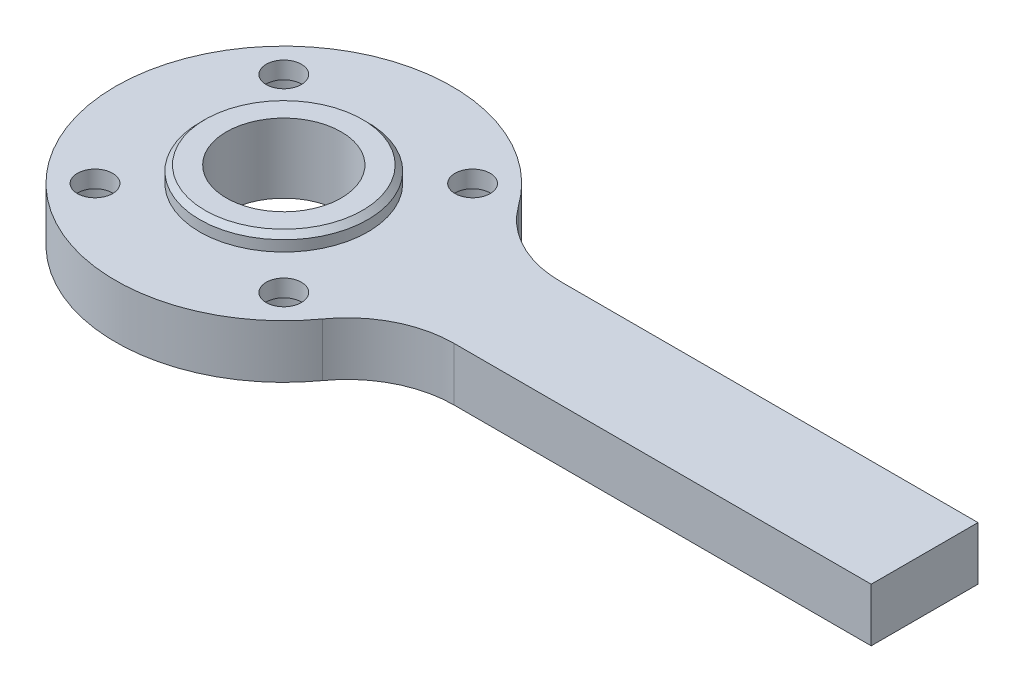
SolidWorks part; units mm, degrees
ref_plane "前视基准面" through (0, 0, 0) normal (0, 0, 1) x (1, 0, 0)
ref_plane "上视基准面" through (0, 0, 0) normal (0, 1, 0) x (1, 0, 0)
ref_plane "右视基准面" through (0, 0, 0) normal (1, 0, 0) x (0, 0, -1)
sketch "草图2" plane through (0, 0, 0) normal (0, 1, 0) x (1, 0, 0)
  circle A0 centre (0, 0) radius 31.5
  dimension "D1" = 63
extrude "凸台-拉伸1" add sketch "草图2" along normal blind 10
sketch "草图3" plane through (0, 10, 0) normal (0, 1, 0) x (1, 0, 0)
  circle A0 centre (0, 0) radius 15.75
  point P3 (0, 0)
  dimension "D1" = 31.5
extrude "凸台-拉伸2" add sketch "草图3" along normal blind 3 contours A0
sketch "草图4" plane through (0, 0, 0) normal (0, -1, 0) x (-1, 0, 0)
  circle A0 centre (0, 0) radius 10.75
  dimension "D1" = 21.5
sketch "草图5" plane through (0, 0, 0) normal (0, -1, 0) x (1, 0, 0)
  line L0 (-34.9596, 0) -> (37.3818, 0) construction
  line L1 (0, -38.4717) -> (0, 38.4717) construction
  line L2 (0, 0) -> (32.0614, 32.0614) construction
  circle A0 centre (17.6777, 17.6777) radius 3.3
  circle A1 centre (17.6777, 17.6777) radius 5.5
  circle A2 centre (0, 0) radius 25
  circle A3 centre (-17.6777, 17.6777) radius 3.3
  circle A4 centre (-17.6777, 17.6777) radius 5.5
  circle A5 centre (-17.6777, -17.6777) radius 3.3
  circle A6 centre (-17.6777, -17.6777) radius 5.5
  circle A7 centre (17.6777, -17.6777) radius 3.3
  circle A8 centre (17.6777, -17.6777) radius 5.5
  point P10 (17.6777, 17.6777)
  point P12 (0, 0.2642)
  dimension "D2" = 6.6
  dimension "D3" = 11
  dimension "D4" = 50
  dimension "D1" = 45
extrude "切除-拉伸2" cut sketch "草图5" against normal through all contours A3 | A0 | A5 | A7
extrude "切除-拉伸3" cut sketch "草图5<3>" against normal blind 6.8 contours A4 | A1 | A6 | A8
sketch "草图5<3>" plane through (0, 0, 0) normal (0, -1, 0) x (1, 0, 0) same geometry as "草图5"
sketch "草图6" plane through (0, 0, 0) normal (1, 0, 0) x (0, 0, -1)
  line L0 (-31.5, 0) -> (31.5, 0) construction
  line L1 (-10, 10) -> (10, 10)
  line L2 (-10, 10) -> (-10, 0)
  line L3 (-10, 0) -> (10, 0)
  line L4 (10, 10) -> (10, 0)
  line L5 (-10, 10) -> (10, 0) construction
  line L6 (-10, 0) -> (10, 10) construction
  point P0 (0, 5)
  point P5 (0, 4.9003)
  dimension "D1" = 10
  dimension "D2" = 20
extrude "凸台-拉伸3" add sketch "草图6" along normal blind 120
extrude "切除-拉伸4" cut sketch "草图4" against normal through all contours A0
chamfer "倒角1" distance 1 angle 45 1 edges at (0, 13, 15.75)
fillet "圆角1" radius 20 1 edges at (29.8706, 5, -10)
fillet "圆角2" radius 20 1 edges at (29.8706, 5, 10)
